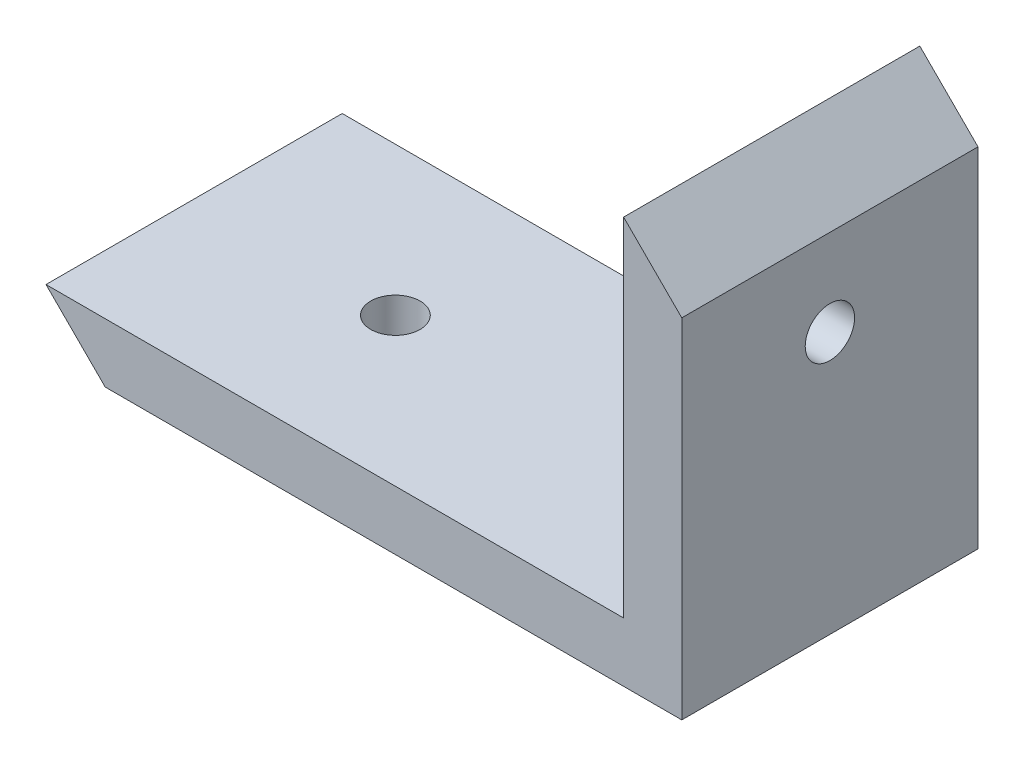
SolidWorks part; units mm, degrees
ref_plane "Front Plane" through (0, 0, 0) normal (0, 0, 1) x (1, 0, 0)
ref_plane "Top Plane" through (0, 0, 0) normal (0, 1, 0) x (1, 0, 0)
ref_plane "Right Plane" through (0, 0, 0) normal (1, 0, 0) x (0, 0, -1)
sketch "Çizim1" plane through (0, 0, 0) normal (0, 1, 0) x (1, 0, 0)
  line L1 (-27.0783, 12.0346) -> (32.9217, 12.0346)
  line L2 (-27.0783, 12.0346) -> (-27.0783, -17.9654)
  line L3 (-27.0783, -17.9654) -> (32.9217, -17.9654)
  line L4 (32.9217, 12.0346) -> (32.9217, -17.9654)
extrude "Yükseklik-Ekstrüzyon1" add sketch "Çizim1" along normal blind 30 contours L2 L1 L4 L3
sketch "Çizim2" plane through (0, 0, 17.9654) normal (0, 0, 1) x (1, 0, 0)
  line L0 (-27.0783, 0) -> (32.9217, 30)
  line L1 (32.9217, 30) -> (-27.0783, 30)
  line L2 (-27.0783, 30) -> (-27.0783, 0)
extrude "Kes-Ekstrüzyon1" cut sketch "Çizim2" against normal blind 30
sketch "Çizim3" plane through (0, 0, 17.9654) normal (0, 0, 1) x (1, 0, 0)
  line L2 (29.3862, 3.5977) -> (-31.4958, 3.5977)
  line L3 (29.3862, 3.5977) -> (29.3862, 34.6436)
  line L4 (29.3862, 34.6436) -> (-31.4958, 34.6436)
  line L5 (-31.4958, 3.5977) -> (-31.4958, 34.6436)
extrude "Kes-Ekstrüzyon2" cut sketch "Çizim3" against normal blind 68 contours L3 L2 L5 L4
sketch "Çizim5" plane through (29.3862, 0, 0) normal (-1, 0, 0) x (0, 0, 1)
  line L0 (17.9654, 28.2322) -> (-12.0346, 3.5977) construction
  circle A0 centre (2.9654, 15.9149) radius 1.5
extrude "Kes-Ekstrüzyon3" cut sketch "Çizim5" against normal blind 68 contours A0
sketch "Çizim6" plane through (29.3862, 0, 0) normal (-1, 0, 0) x (0, 0, 1)
  line L0 (-12.0346, 30) -> (17.9654, 30) construction
  line L6 (-12.0346, 0) -> (17.9654, 0) construction
  line L7 (-12.0346, 30) -> (-6.0346, 30)
  line L8 (-12.0346, 30) -> (-12.0346, 0)
  line L9 (-12.0346, 0) -> (-6.0346, 0)
  line L10 (-6.0346, 30) -> (-6.0346, 0)
  line L11 (17.9654, 30) -> (11.9654, 30)
  line L12 (17.9654, 30) -> (17.9654, 0)
  line L13 (17.9654, 0) -> (11.9654, 0)
  line L14 (11.9654, 30) -> (11.9654, 0)
extrude "Kes-Ekstrüzyon6" cut sketch "Çizim6" against normal blind 68 and the other way blind 68
sketch "Çizim7" plane through (0, 3.5977, 0) normal (0, 1, 0) x (1, 0, 0)
  line L0 (-19.883, 6.0346) -> (32.9217, -11.9654) construction
  circle A0 centre (6.5194, -2.9654) radius 1.5
extrude "Kes-Ekstrüzyon7" cut sketch "Çizim7" against normal blind 68
sketch "Çizim8" plane through (0, 3.5977, 0) normal (0, 1, 0) x (1, 0, 0)
  line L0 (29.3862, 6.0346) -> (-19.883, 6.0346) construction
  line L1 (32.9217, -11.9654) -> (-5.7137, -11.9654)
  line L2 (32.9217, -11.9654) -> (32.9217, 6.0346)
  line L3 (32.9217, 6.0346) -> (-5.7137, 6.0346)
  line L4 (-5.7137, -11.9654) -> (-5.7137, 6.0346)
  line L6 (-5.7137, -11.9654) -> (-27.0783, -11.9654)
  line L7 (-5.7137, -11.9654) -> (-5.7137, 6.0346)
  line L8 (-5.7137, 6.0346) -> (-27.0783, 6.0346)
  line L9 (-27.0783, -11.9654) -> (-27.0783, 6.0346)
extrude "Kes-Ekstrüzyon8" cut sketch "Çizim8" against normal blind 68 contours L7 L6 L9 L8
sketch "Çizim9" plane through (0, 0, 11.9654) normal (0, 0, 1) x (1, 0, 0)
  line L0 (-5.7137, 3.5977) -> (-2.1161, 0)
  line L1 (-5.7137, 0) -> (32.9217, 0) construction
  line L2 (-2.1161, 0) -> (-5.7137, 0)
  line L3 (-5.7137, 0) -> (-5.7137, 3.5977)
extrude "Kes-Ekstrüzyon9" cut sketch "Çizim9" against normal blind 68
sketch "Çizim10" plane through (0, 0, 11.9654) normal (0, 0, 1) x (1, 0, 0)
  line L0 (29.3862, 28.2322) -> (32.9217, 24.6967)
  line L1 (32.9217, 30) -> (32.9217, 0) construction
  line L2 (32.9217, 24.6967) -> (29.3862, 24.6967)
  line L3 (29.3862, 28.2322) -> (29.3862, 3.5977) construction
  line L4 (29.3862, 24.6967) -> (29.3862, 28.2322)
extrude "Kes-Ekstrüzyon10" cut sketch "Çizim10" against normal blind 68
sketch "Çizim11" plane through (0, 0, 11.9654) normal (0, 0, 1) x (1, 0, 0)
  line L0 (29.3862, 28.2322) -> (32.9217, 30)
  line L1 (32.9217, 30) -> (32.9217, 24.6967)
  line L2 (32.9217, 24.6967) -> (29.3862, 28.2322)
extrude "Kes-Ekstrüzyon11" cut sketch "Çizim11" against normal blind 68
sketch "Çizim12" plane through (0, 0, 11.9654) normal (0, 0, 1) x (1, 0, 0)
  line L0 (29.3862, 24.6967) -> (32.9217, 21.1612)
  line L1 (32.9217, 24.6967) -> (32.9217, 0) construction
  line L2 (32.9217, 21.1612) -> (32.9217, 24.6967)
  line L3 (32.9217, 24.6967) -> (29.3862, 24.6967)
extrude "Kes-Ekstrüzyon12" cut sketch "Çizim12" against normal blind 68
